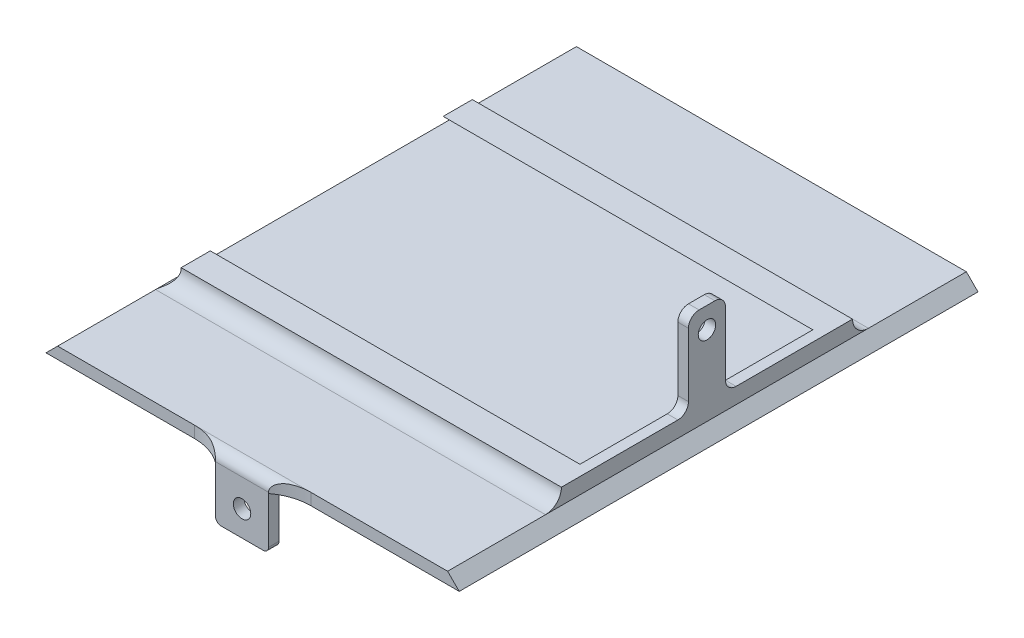
SolidWorks part; units mm, degrees
ref_plane "Front Plane" through (0, 0, 0) normal (0, 0, 1) x (1, 0, 0)
ref_plane "Top Plane" through (0, 0, 0) normal (0, 1, 0) x (1, 0, 0)
ref_plane "Right Plane" through (0, 0, 0) normal (1, 0, 0) x (0, 0, -1)
sketch "Sketch1" plane through (0, 0, 0) normal (0, 0, 1) x (1, 0, 0)
  line L0 (40, 0) -> (-40, 0) construction
  line L1 (-40, 0) -> (-37, 3) construction
  line L2 (-37, 3) -> (37, 3) construction
  line L3 (37, 3) -> (40, 0) construction
  line L4 (36.8343, 2.6) -> (39.0343, 0.4)
  line L5 (39.0343, 0.4) -> (-39.0343, 0.4)
  line L6 (-39.0343, 0.4) -> (-36.8343, 2.6)
  line L7 (-36.8343, 2.6) -> (36.8343, 2.6)
  point P4 (0, 0)
  dimension "D1" = 45
  dimension "D2" = 45
  dimension "D3" = 3
  dimension "D4" = 80
  dimension "D5" = 0.4
extrude "Boss-Extrude1" add sketch "Sketch1" against normal blind 98
sketch "Sketch3" plane through (0, 2.6, 0) normal (0, 1, 0) x (1, 0, 0)
  line L0 (36.8343, 0) -> (-36.8343, 0) construction
  line L1 (-5, -2) -> (5, -2)
  line L2 (-5, -2) -> (-5, 0)
  line L3 (-5, 0) -> (5, 0)
  line L4 (5, -2) -> (5, 0)
  line L5 (-5, -2) -> (5, 0) construction
  line L6 (-5, 0) -> (5, -2) construction
  point P0 (0, -1)
  dimension "D1" = 10
  dimension "D2" = 2
extrude "Boss-Extrude2" add sketch "Sketch3" against normal blind 12
sketch "Sketch4" plane through (0, 0, 2) normal (0, 0, 1) x (1, 0, 0)
  line L0 (5, 0.4) -> (39.0343, 0.4) construction
  circle A0 centre (0, -4.6) radius 1.65
  dimension "D1" = 3.3
  dimension "D2" = 5
extrude "Cut-Extrude1" cut sketch "Sketch4" against normal up to surface (2 mm away) up to face at (0, -4.5, 0)
fillet "Fillet1" radius 10 2 edges at (5, 1.5, 0) (-5, 1.5, 0)
fillet "Fillet2" radius 2 1 edges at (0, 2.6, 2)
fillet "Fillet3" radius 0.8 1 edges at (0, 0.4, 0)
fillet "Fillet4" radius 1 2 edges at (5, -9.4, 1) (-5, -9.4, 1)
ref_plane "Plane1" through (0, 0, 0) normal (1, 0, 0) x (0, 0, -1)
sketch "Sketch5" plane through (0, 0, 0) normal (1, 0, 0) x (0, 0, -1)
  line L0 (21.5, 5.6) -> (21.5, 2.6)
  line L2 (76.5, 2.6) -> (76.5, 5.6)
  line L3 (76.5, 5.6) -> (71, 5.6)
  line L4 (71, 5.6) -> (74, 2.6)
  line L6 (24, 2.6) -> (27, 5.6)
  line L7 (27, 5.6) -> (21.5, 5.6)
  line L8 (24, 2.6) -> (21.5, 2.6)
  line L9 (98, 2.6) -> (0, 2.6) construction
  line L10 (74, 2.6) -> (76.5, 2.6)
  line L11 (24, 2.6) -> (74, 2.6) construction
  line L12 (0, 0.4) -> (0, 2.6) construction
  point P2 (49, 2.6)
  point P9 (49, 2.6)
  dimension "D1" = 50
  dimension "D2" = 3
  dimension "D3" = 49
  dimension "D4" = 45
  dimension "D5" = 2.5
  dimension "D6" = 2.5
  dimension "D7" = 45
extrude "Boss-Extrude3" add sketch "Sketch5" along normal up to vertex (36.8343 mm away) and the other way blind 35 up to point (36.8343, 2.6, -98)
sketch "Sketch10" plane through (0, 0, -21.5) normal (0, 0, 1) x (1, 0, 0)
  line L0 (36.8343, 5.6) -> (36.8343, 2.6) construction
  line L1 (34.8343, 5.6) -> (36.8343, 5.6)
  line L2 (34.8343, 5.6) -> (34.8343, 2.6)
  line L3 (34.8343, 2.6) -> (36.8343, 2.6)
  line L4 (36.8343, 5.6) -> (36.8343, 2.6)
  line L5 (34.8343, 5.6) -> (36.8343, 2.6) construction
  line L6 (34.8343, 2.6) -> (36.8343, 5.6) construction
  line L7 (-35, 5.6) -> (36.8343, 5.6) construction
  line L8 (-35, 2.6) -> (36.8343, 2.6) construction
  point P0 (35.8343, 4.1)
  dimension "D1" = 2
extrude "Boss-Extrude6" add sketch "Sketch10" against normal up to surface (49.5 mm away) up to face at (0.9172, 4.1, -72.5)
sketch "Sketch11" plane through (34.8343, 0, 0) normal (-1, 0, 0) x (0, 0, 1)
  line L0 (-71, 5.6) -> (-27, 5.6) construction
  line L1 (-52.5, 21.6) -> (-45.5, 21.6)
  line L2 (-52.5, 21.6) -> (-52.5, 5.6)
  line L3 (-52.5, 5.6) -> (-45.5, 5.6)
  line L4 (-45.5, 21.6) -> (-45.5, 5.6)
  line L5 (-52.5, 21.6) -> (-45.5, 5.6) construction
  line L6 (-52.5, 5.6) -> (-45.5, 21.6) construction
  line L8 (-74, 2.6) -> (-24, 2.6) construction
  circle A0 centre (-49, 17.6) radius 1.65
  point P0 (-49, 13.6)
  dimension "D4" = 3.3
  dimension "D1" = 16
  dimension "D2" = 7
  dimension "D3" = 22
  dimension "D5" = 15
extrude "Boss-Extrude7" add sketch "Sketch11" against normal up to surface (2 mm away) up to face at (36.8343, 4.1, -49)
fillet "Fillet5" radius 2 4 edges at (35.8343, 21.6, -52.5) (35.8343, 21.6, -45.5) (35.8343, 5.6, -45.5) (35.8343, 5.6, -52.5)
fillet "Fillet6" radius 1 1 edges at (34.8343, 2.6, -49)
fillet "Fillet7" radius 3 4 edges at (-35, 2.6, -75.25) (-35, 2.6, -22.75) (0.9172, 2.6, -21.5) (0.9172, 2.6, -76.5)
